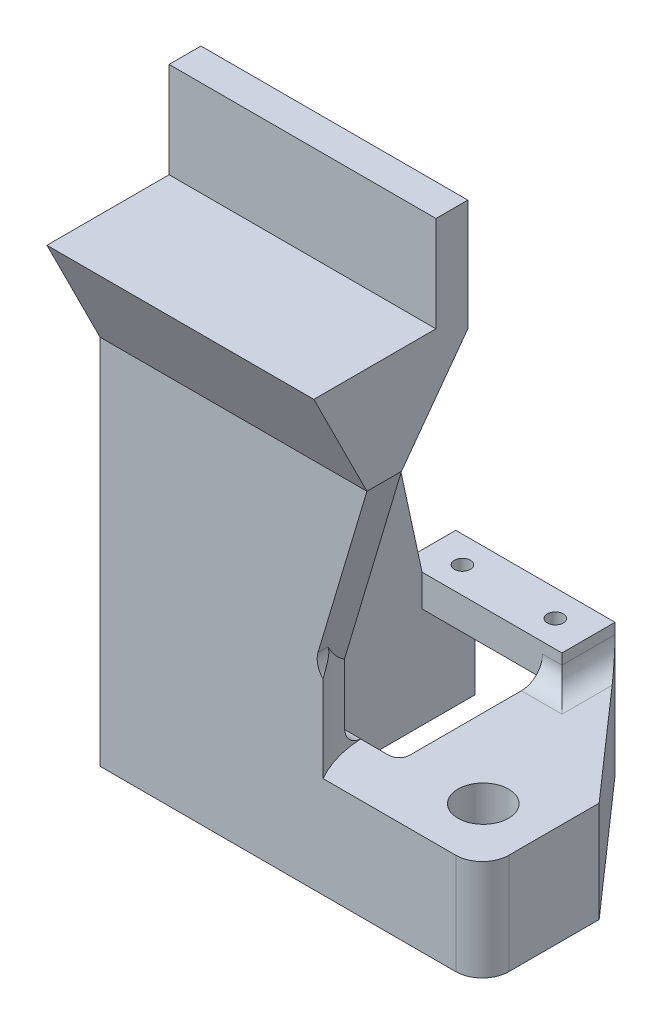
SolidWorks part; units mm, degrees
ref_plane "Front Plane" through (0, 0, 0) normal (0, 0, 1) x (1, 0, 0)
ref_plane "Top Plane" through (0, 0, 0) normal (0, 1, 0) x (1, 0, 0)
ref_plane "Right Plane" through (0, 0, 0) normal (1, 0, 0) x (0, 0, -1)
sketch "Sketch1" plane through (0, 0, 0) normal (0, 1, 0) x (1, 0, 0)
  line L0 (-5.7502, 0) -> (11.7498, 0) construction
  circle A0 centre (-5.7502, 0) radius 1.5 construction
  circle A1 centre (11.7498, 0) radius 1.5 construction
  dimension "D1" = 3
  dimension "D2" = 17.5
sketch "Sketch2" plane through (0, 0, 0) normal (0, 1, 0) x (1, 0, 0)
  line L0 (2.9998, -5) -> (2.9998, 5) construction
  line L1 (-12.0002, -5) -> (17.9998, -5)
  line L2 (-12.0002, -5) -> (-12.0002, 5)
  line L3 (-12.0002, 5) -> (17.9998, 5)
  line L4 (17.9998, -5) -> (17.9998, 5)
  line L5 (-5.7502, 0) -> (11.7498, 0) construction
  line L6 (-12.0002, 0) -> (17.9998, 0) construction
  point P6 (2.9998, 0)
  point P11 (2.9998, 0)
  dimension "D1" = 30
  dimension "D2" = 10
extrude "Boss-Extrude1" add sketch "Sketch2" along normal blind 25
sketch "Sketch3" plane through (0, 0, 5) normal (0, 0, 1) x (1, 0, 0)
  line L0 (2.9998, 25) -> (2.9998, 0) construction
  line L1 (-12.0002, 25) -> (17.9998, 25) construction
  line L2 (-5.7502, 0) -> (11.7498, 0) construction
  line L3 (-12.0002, 12.5) -> (17.9998, 12.5) construction
  line L4 (-12.0002, 25) -> (-12.0002, 0) construction
  line L5 (17.9998, 25) -> (17.9998, 0) construction
  line L6 (-12.0002, 0) -> (17.9998, 0) construction
  line L7 (-8.3502, 0) -> (14.3498, 0)
  line L8 (-8.3502, 0) -> (-8.3502, 19)
  line L9 (-8.3502, 19) -> (14.3498, 19)
  line L10 (14.3498, 0) -> (14.3498, 19)
  line L11 (-8.3502, 0) -> (14.3498, 19) construction
  line L12 (-8.3502, 19) -> (14.3498, 0) construction
  point P12 (2.9998, 12.5)
  dimension "D1" = 19
  dimension "D2" = 22.7
extrude "Cut-Extrude1" cut sketch "Sketch3" against normal through all
sketch "Sketch4" plane through (0, 0, 0) normal (0, -1, 0) x (1, 0, 0)
  circle A0 centre (-5.7502, 0) radius 1.5
  circle A1 centre (11.7498, 0) radius 1.5
extrude "Cut-Extrude2" cut sketch "Sketch4" against normal through all
sketch "Sketch5" plane through (0, 0, 5) normal (0, 0, 1) x (1, 0, 0)
  line L0 (13.2498, 0) -> (10.2498, 0) construction
  line L1 (17.9998, 19) -> (14.3498, 19)
  line L2 (17.9998, 19) -> (17.9998, 0)
  line L3 (17.9998, 0) -> (14.3498, 0)
  line L4 (14.3498, 19) -> (14.3498, 0)
  line L5 (14.3498, 0) -> (14.3498, 19) construction
  line L6 (14.3498, 19) -> (-8.3502, 19) construction
extrude "Boss-Extrude2" add sketch "Sketch5" along normal blind 37
sketch "Sketch6" plane through (0, 0, 5) normal (0, 0, 1) x (1, 0, 0)
  line L0 (-8.3502, 19) -> (-8.3502, 0) construction
  line L1 (-12.0002, 0) -> (-8.3502, 0)
  line L2 (-12.0002, 0) -> (-12.0002, 19)
  line L3 (-12.0002, 19) -> (-8.3502, 19)
  line L4 (-8.3502, 0) -> (-8.3502, 19)
  line L6 (14.3498, 19) -> (-8.3502, 19) construction
extrude "Boss-Extrude3" add sketch "Sketch6" along normal blind 37
sketch "Sketch11" plane through (14.3498, 0, 0) normal (-1, 0, 0) x (0, 0, 1)
  line L0 (42, 19) -> (5, 19) construction
  line L1 (42, 0) -> (32, 0)
  line L2 (42, 0) -> (42, 19)
  line L3 (42, 19) -> (32, 19)
  line L4 (32, 0) -> (32, 19)
  dimension "D1" = 10
extrude "Boss-Extrude7" add sketch "Sketch11" along normal up to surface (22.7 mm away) up to face at (-8.3502, 11.4, 15.8)
sketch "Sketch12" plane through (0, 0, 0) normal (0, -1, 0) x (1, 0, 0)
  line L0 (-8.3502, 32) -> (14.3498, 32) construction
  line L1 (0.3998, 32) -> (5.5998, 32)
  line L2 (0.3998, 32) -> (0.3998, 37.2)
  line L3 (0.3998, 37.2) -> (5.5998, 37.2)
  line L4 (5.5998, 32) -> (5.5998, 37.2)
  line L5 (0.3998, 34.6) -> (-8.3502, 34.6) construction
  line L6 (-8.3502, 34.6) -> (-8.3502, 32) construction
  line L7 (5.5998, 34.6) -> (14.3498, 34.6) construction
  line L8 (14.3498, 34.6) -> (14.3498, 32) construction
  dimension "D1" = 5.2
  dimension "D2" = 5.2
extrude "Cut-Extrude4" cut sketch "Sketch12" against normal blind 11.2
sketch "Sketch13" plane through (0, 11.2, 0) normal (0, -1, 0) x (1, 0, 0)
  line L0 (5.5998, 32) -> (5.5998, 37.2) construction
  line L1 (5.5998, 37.2) -> (0.3998, 37.2) construction
  circle A0 centre (3.0998, 34.7) radius 1.4
  dimension "D3" = 2.8
  dimension "D1" = 2.5
  dimension "D2" = 2.5
extrude "Cut-Extrude5" [suppressed] cut sketch "Sketch13" against normal through all
sketch "Sketch14" plane through (17.9998, 0, 0) normal (1, 0, 0) x (0, 0, -1)
  line L0 (-42, 19) -> (-5, 19) construction
  line L1 (-42, 0) -> (-20, 0)
  line L2 (-42, 0) -> (-42, 19)
  line L3 (-42, 19) -> (-20, 19)
  line L4 (-20, 0) -> (-20, 19)
  dimension "D1" = 22
extrude "Boss-Extrude8" add sketch "Sketch14" along normal blind 22
sketch "Sketch15" plane through (0, 19, 0) normal (0, 1, 0) x (1, 0, 0)
  line L0 (17.9998, -20) -> (17.9998, -42) construction
  line L1 (39.9998, -42) -> (-12.0002, -42) construction
  line L2 (17.9998, -31) -> (39.9998, -31) construction
  line L3 (39.9998, -20) -> (39.9998, -42) construction
  circle A0 centre (29.1798, -31) radius 4.77
  dimension "D1" = 9.54
  dimension "D2" = 11.18
extrude "Cut-Extrude6" cut sketch "Sketch15" against normal through all
sketch "Sketch16" plane through (0, 19, 0) normal (0, 1, 0) x (1, 0, 0)
  line L1 (-12.0002, -42) -> (9.9998, -42)
  line L2 (-12.0002, -42) -> (-12.0002, -35.5)
  line L3 (-12.0002, -35.5) -> (7.5321, -35.5)
  line L5 (39.9998, -42) -> (-12.0002, -42) construction
  line L6 (-8.3502, -32) -> (14.3498, -32) construction
  arc A0 (7.5321, -35.5) -> (9.9998, -42) centre (29.1798, -31) ccw
  circle A1 centre (29.1798, -31) radius 4.77 construction
  dimension "D1" = 22
  dimension "D2" = 3.5
extrude "Boss-Extrude9" add sketch "Sketch16" along normal blind 15
sketch "Sketch18" plane through (0, 19, 0) normal (0, 1, 0) x (1, 0, 0)
  line L0 (17.9998, -20) -> (17.9998, 5)
  line L2 (39.9998, -20) -> (17.9998, -20)
  line L3 (17.9998, 5) -> (39.9998, -20)
extrude "Boss-Extrude11" add sketch "Sketch18" against normal up to surface (19 mm away) up to face at (29.1798, 0, 35.77)
sketch "Sketch19" plane through (0, 0, 42) normal (0, 0, 1) x (1, 0, 0)
  line L1 (-32.0002, 90) -> (18.2659, 90)
  line L2 (18.2659, 90) -> (18.2659, 70)
  line L3 (18.2659, 70) -> (7.5321, 34)
  line L4 (7.5321, 34) -> (-12.0002, 34)
  line L5 (-12.0002, 0) -> (39.9998, 0) construction
  line L8 (-32.0002, 90) -> (-32.0002, 0)
  line L9 (-2.2341, 70) -> (-2.2341, 34) construction
  line L10 (-12.0002, 34) -> (9.9998, 34) construction
  line L12 (-32.0002, 0) -> (-12.0002, 0)
  line L13 (-12.0002, 0) -> (-12.0002, 34)
  point P14 (-2.2341, 34)
  dimension "D1" = 70
  dimension "D2" = 20
  dimension "D3" = 20.5
  dimension "D4" = 20
extrude "Boss-Extrude12" add sketch "Sketch19" against normal up to surface (6.5 mm away) up to face at (-2.2341, 26.5, 35.5)
sketch "Sketch22" plane through (18.2659, 0, 0) normal (1, 0, 0) x (0, 0, -1)
  line L0 (-35.5, 90) -> (-29, 90)
  line L1 (-29, 90) -> (-29, 108)
  line L2 (-29, 108) -> (-23, 108)
  line L3 (-23, 108) -> (-23, 87)
  line L4 (-23, 87) -> (-35.5, 70)
  line L5 (-35.5, 70) -> (-35.5, 34) construction
  line L6 (-35.5, 90) -> (-35.5, 70) construction
  line L7 (-35.5, 70) -> (-35.5, 90)
  line L8 (-42, 90) -> (-52.0022, 90)
  line L12 (-52.0022, 90) -> (-42, 70)
  line L13 (-42, 34) -> (-42, 70) construction
  line L14 (-42, 90) -> (-42, 70)
  line L15 (-35.5, 70) -> (-42, 70) construction
  line L16 (-35.5, 70) -> (-42, 70) construction
  dimension "D1" = 6
  dimension "D2" = 6.5
  dimension "D3" = 3
  dimension "D4" = 18
  dimension "D5" = 36.327
  dimension "D7" = 10.0022
extrude "Boss-Extrude14" add sketch "Sketch22" against normal up to surface (50.2662 mm away) up to face at (-32.0002, 45, 38.75)
sketch "Sketch21" plane through (0, 0, 0) normal (0, -1, 0) x (1, 0, 0)
  line L0 (-12.0002, -5) -> (-12.0002, 35.5) construction
  line L1 (-12.0002, 18.08) -> (-8.3502, 18.08)
  line L2 (-12.0002, 18.08) -> (-12.0002, 23.53)
  line L3 (-12.0002, 23.53) -> (-8.3502, 23.53)
  line L4 (-8.3502, 18.08) -> (-8.3502, 23.53)
  line L5 (-8.3502, -5) -> (-8.3502, 32) construction
  line L7 (-5.7502, 0) -> (11.7498, 0) construction
  dimension "D1" = 18.08
  dimension "D2" = 5.45
extrude "Cut-Extrude7" cut sketch "Sketch21" against normal blind 3
sketch "Sketch23" plane through (-12.0002, 0, 0) normal (-1, 0, 0) x (0, 0, 1)
  line L1 (23, 87) -> (35.5, 70)
  line L2 (35.5, 70) -> (35.5, 19)
  line L3 (35.5, 19) -> (5, 19)
  line L4 (5, 19) -> (5, 25)
  line L5 (5, 25) -> (23, 108)
  line L6 (23, 108) -> (23, 87)
extrude "Boss-Extrude15" add sketch "Sketch23" against normal up to surface (3.65 mm away) up to face at (-8.3502, 7, 15.8022)
sketch "Sketch24" plane through (0, 0, 0) normal (0, -1, 0) x (1, 0, 0)
  line L0 (-32.0002, 35.5) -> (-12.0002, -5)
  line L1 (-12.0002, -5) -> (-12.0002, 4.0338)
  line L2 (-12.0002, -5) -> (-12.0002, 18.08) construction
  line L4 (-12.0002, 35.5) -> (-32.0002, 35.5) construction
  line L5 (-27.5391, 35.5) -> (-32.0002, 35.5)
  line L6 (-27.5391, 35.5) -> (-23.6033, 27.53)
  line L10 (-16.9613, 14.08) -> (-12.0002, 4.0338)
  line L11 (-16.9613, 14.08) -> (-12.0002, 14.08)
  line L12 (-12.0002, 14.08) -> (-12.0002, 18.08)
  line L13 (-12.0002, 18.08) -> (-19.7502, 18.08)
  line L14 (-19.7502, 18.08) -> (-19.7502, 23.53)
  line L15 (-19.7502, 23.53) -> (-12.0002, 23.53)
  line L16 (-12.0002, 23.53) -> (-12.0002, 27.53)
  line L17 (-12.0002, 23.53) -> (-12.0002, 35.5) construction
  line L18 (-12.0002, 27.53) -> (-23.6033, 27.53)
  line L19 (-27.5391, 35.5) -> (-12.0002, 4.0338) construction
  line L20 (-12.0002, 23.53) -> (-12.0002, 18.08) construction
  point P4 (0, 0)
  point P13 (-18.2108, 23.53)
  point P15 (0, 0)
  point P25 (-18.9366, 23.53)
  dimension "D1" = 4
  dimension "D2" = 4
  dimension "D3" = 4
  dimension "D4" = 7.75
extrude "Boss-Extrude16" add sketch "Sketch24" against normal blind 5
fillet "Fillet1" radius 5 1 edges at (39.9998, 9.5, 42)
fillet "Fillet3" radius 2 2 edges at (-8.3502, 9.5, 32) (14.3498, 9.5, 32)
fillet "Fillet5" radius 4 1 edges at (7.5321, 34, 38.75)
fillet "Fillet7" radius 1 6 edges at (-12.0002, 2.5, 27.53) (-23.6033, 2.5, 27.53) (-27.5391, 2.5, 35.5) (-12.0002, 2.5, 14.08) (-16.9613, 2.5, 14.08) (-12.0002, 2.5, 4.0338)
fillet "Fillet8" radius 4 13 edges at (16.1748, 19, 5) (17.9998, 19, 0) (-0.4091, 19, 35.5) (-8.3502, 44.5, 35.5) (-12.0002, 35, 35.5) (-8.3502, 97.5, 23) (-12.0002, 97.5, 23) (-12.0002, 78.5, 29.25) (-8.3502, 78.5, 29.25) (-28.9651, 5, 35.5) (-12.0002, 5, 1.6586) (-12.0002, 5, 26.03) (-12.0002, 5, 15.58)
